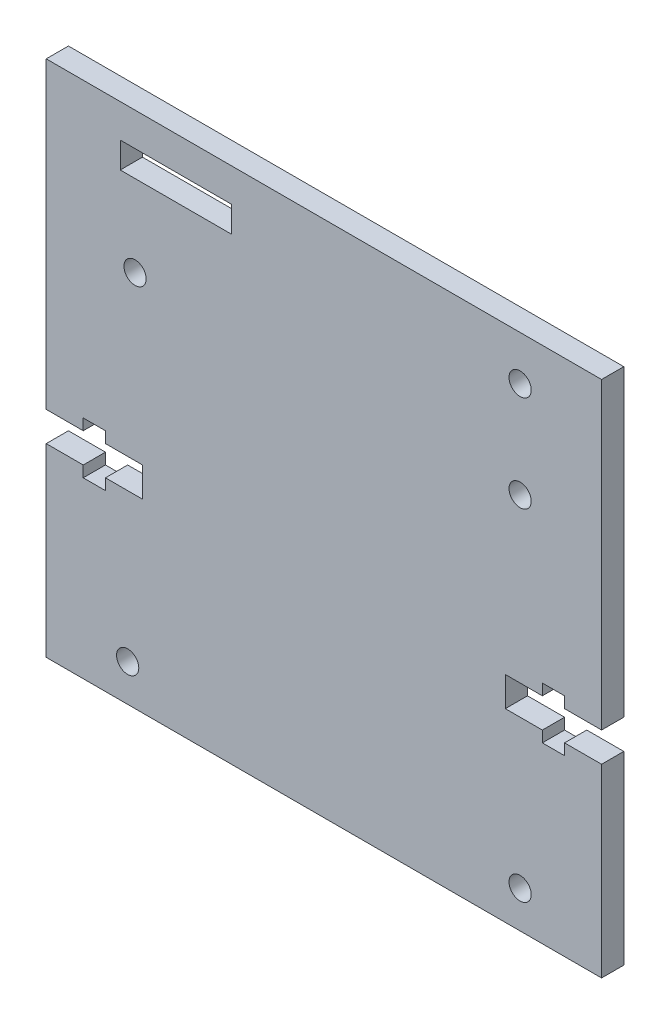
SolidWorks part; units mm, degrees
ref_plane "Plan de face" through (0, 0, 0) normal (0, 0, 1) x (1, 0, 0)
ref_plane "Plan de dessus" through (0, 0, 0) normal (0, 1, 0) x (1, 0, 0)
ref_plane "Plan de droite" through (0, 0, 0) normal (1, 0, 0) x (0, 0, -1)
sketch "Esquisse1" plane through (0, 0, 0) normal (0, 0, 1) x (1, 0, 0)
  line L0 (-27.5, 18.7253) -> (-12.5, 18.7253)
  line L1 (-37.5, -46.7747) -> (37.5, -46.7747)
  line L2 (-37.5, -46.7747) -> (-37.5, 23.2253)
  line L3 (-37.5, 23.2253) -> (37.5, 23.2253)
  line L4 (37.5, -46.7747) -> (37.5, 23.2253)
  line L9 (-27.5, 18.7253) -> (-27.5, 15.2253)
  line L10 (-27.5, 15.2253) -> (-12.5, 15.2253)
  line L11 (-12.5, 18.7253) -> (-12.5, 15.2253)
  line L12 (37.5, -21.7747) -> (32.5, -21.7747)
  line L13 (32.5, -21.7747) -> (32.5, -23.2747)
  line L14 (32.5, -23.2747) -> (29.5, -23.2747)
  line L15 (29.5, -23.2747) -> (29.5, -21.7747)
  line L16 (29.5, -21.7747) -> (24.5, -21.7747)
  line L17 (24.5, -21.7747) -> (24.5, -17.7747)
  line L18 (24.5, -17.7747) -> (29.5, -17.7747)
  line L19 (29.5, -17.7747) -> (29.5, -16.2747)
  line L20 (29.5, -16.2747) -> (32.5, -16.2747)
  line L21 (32.5, -16.2747) -> (32.5, -17.7747)
  line L22 (32.5, -17.7747) -> (37.5, -17.7747)
  line L23 (37.5, -17.7747) -> (37.5, -21.7747)
  line L24 (0, -46.7747) -> (0, 46.7747) construction
  line L25 (-37.5, -17.7747) -> (-37.5, -21.7747)
  line L26 (-32.5, -17.7747) -> (-37.5, -17.7747)
  line L27 (-32.5, -16.2747) -> (-32.5, -17.7747)
  line L28 (-29.5, -16.2747) -> (-32.5, -16.2747)
  line L29 (-29.5, -17.7747) -> (-29.5, -16.2747)
  line L30 (-24.5, -17.7747) -> (-29.5, -17.7747)
  line L31 (-24.5, -21.7747) -> (-24.5, -17.7747)
  line L32 (-29.5, -21.7747) -> (-24.5, -21.7747)
  line L33 (-29.5, -23.2747) -> (-29.5, -21.7747)
  line L34 (-32.5, -23.2747) -> (-29.5, -23.2747)
  line L35 (-32.5, -21.7747) -> (-32.5, -23.2747)
  line L36 (-37.5, -21.7747) -> (-32.5, -21.7747)
  circle A0 centre (-26.5, -41.7747) radius 1.5
  circle A1 centre (26.5, -41.7747) radius 1.5
  circle A2 centre (26.5, 4.2253) radius 1.5
  circle A3 centre (26.5, 17.2253) radius 1.5
  circle A4 centre (-25.5, 4.2253) radius 1.5
  dimension "D3" = 3
  dimension "D1" = 70
  dimension "D2" = 75
  dimension "D4" = 5
  dimension "D5" = 11
  dimension "D6" = 11
  dimension "D7" = 6
  dimension "D8" = 19
  dimension "D9" = 12
  dimension "D11" = 4.5
  dimension "D12" = 10
  dimension "D13" = 25
  dimension "D14" = 5
  dimension "D15" = 3
  dimension "D16" = 1.5
  dimension "D17" = 4
  dimension "D18" = 37.5
extrude "Boss.-Extru.1" add sketch "Esquisse1" along normal blind 3 contours L1 L24 L3 L2 L26 L27 L28 L29 L30 L31 L32 L33 L34 L35 L36 L0 L11 L10 L9 A0 A4 | L24 L1 L4 L12 L13 L14 L15 L16 L17 L18 L19 L20 L21 L22 L3 A3 A2 A1 region at (-18.3835, -12.1441, 0) region at (18.3915, -11.6245, 0)
